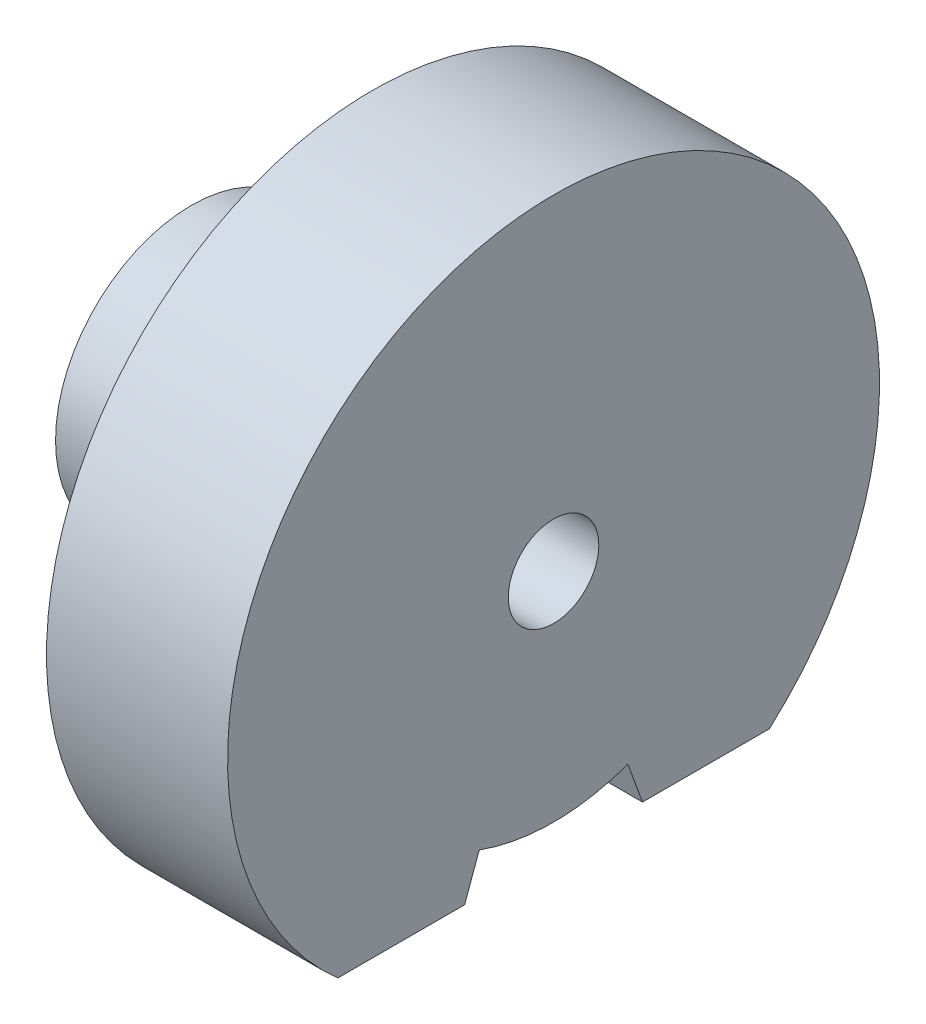
SolidWorks part; units mm, degrees
ref_plane "Plan de face" through (0, 0, 0) normal (0, 0, 1) x (1, 0, 0)
ref_plane "Plan de dessus" through (0, 0, 0) normal (0, 1, 0) x (1, 0, 0)
ref_plane "Plan de droite" through (0, 0, 0) normal (1, 0, 0) x (0, 0, -1)
sketch "Esquisse29" plane through (0, 0, 0) normal (0, 0, 1) x (1, 0, 0)
  line L0 (-2, 0) -> (-5, 0)
  line L1 (5, 0) -> (2, 0)
  line L2 (5, 0) -> (5, -12)
  line L3 (5, -12) -> (-5, -12)
  line L4 (-5, 0) -> (-5, -12)
  line L5 (0, 0) -> (0, -2) construction
  line L6 (-5, 0) -> (5, 0)
  line L7 (-5, 0) -> (-5, 6)
  line L8 (5, 0) -> (5, 6)
  line L9 (-5, 6) -> (5, 6)
  arc A0 (-2, 0) -> (2, 0) centre (0, 0) ccw
  circle A1 centre (0, 0) radius 2
  dimension "D1" = 4
  dimension "D2" = 10
  dimension "D3" = 12
  dimension "D4" = 18
revolve "Révolution2" add sketch "Esquisse29" angle 360 about L3 region at (0, -6.2846, 0)
revolve "Révolution3" add sketch "Esquisse29<3>" angle 320 mid plane about L3 region at (0, 3.2516, 0)
sketch "Esquisse29<3>" plane through (0, 0, 0) normal (0, 0, 1) x (1, 0, 0) same geometry as "Esquisse29"
chamfer "Chanfrein1" distance 10 angle 20 1 edges at (0, -28.9145, -6.1564) first distance on face at (0, -11.4572, 0)
chamfer "Chanfrein3" distance 10 angle 20 1 edges at (0, -28.9145, 6.1564) first distance on face at (0, -10.7592, 0.2349)
sketch "Esquisse30" plane through (5, 0, 0) normal (1, 0, 0) x (0, 0, -1)
  circle A0 centre (0, -12) radius 2.5
  dimension "D1" = 5
extrude "Enlèv. mat.-Extru.1" cut sketch "Esquisse30" against normal blind 10
sketch "Esquisse31" plane through (-5, 0, 0) normal (-1, 0, 0) x (0, 0, 1)
  circle A0 centre (0, -12) radius 7.5
  circle A1 centre (0, -12) radius 2.5 construction
  circle A2 centre (0, -12) radius 2.5
  dimension "D1" = 15
extrude "Boss.-Extru.1" add sketch "Esquisse31" along normal blind 10
sketch "Esquisse32" plane through (0, 0, 0) normal (0, 0, 1) x (1, 0, 0)
  line L0 (-5, -4.5) -> (-5, -19.5) construction
  line L1 (-15, -4.5) -> (-15, -19.5) construction
  line L2 (-5, -4.5) -> (-5, -19.5)
  line L3 (-15, -4.5) -> (-15, -19.5)
  line L4 (-15, -12) -> (-5, -12) construction
  circle A0 centre (-10, -12) radius 1.2313
  dimension "D1" = 2.4626
fillet "Congé1" radius 2 1 edges at (-5, -12, 7.5)
ref_axis "Axe1" through (-15, -12, 0) along (1, 0, 0)
